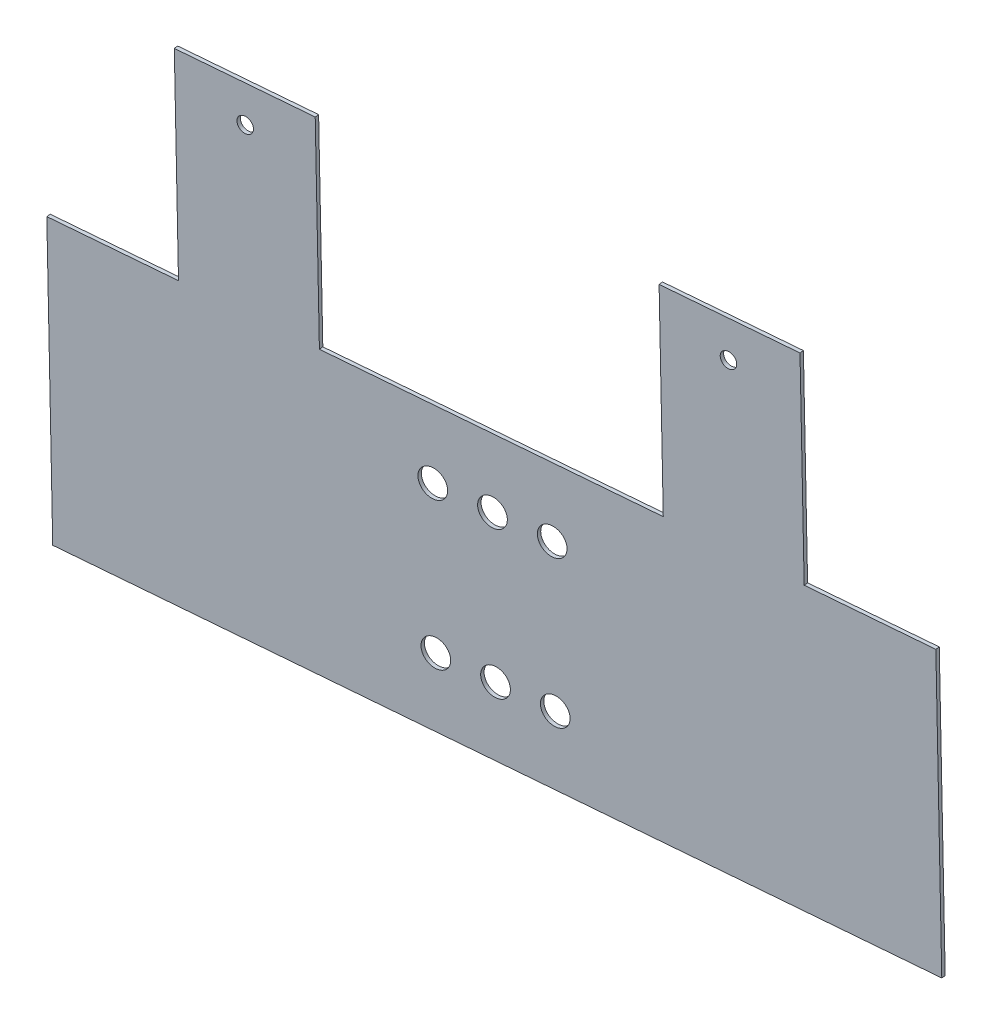
SolidWorks part; units mm, degrees
ref_plane "Front Plane" through (0, 0, 0) normal (0, 0, 1) x (1, 0, 0)
ref_plane "Top Plane" through (0, 0, 0) normal (0, 1, 0) x (1, 0, 0)
ref_plane "Right Plane" through (0, 0, 0) normal (1, 0, 0) x (0, 0, -1)
sketch "Sketch1" plane through (16.9972, -4.1499, 204.6314) normal (-0.0828, 0.0202, -0.9964) x (0.9966, 0.002, -0.0827)
  line L0 (-405.6316, 283.217) -> (-385.6926, 283.217)
  line L1 (-520.3126, 330.217) -> (-500.3736, 330.217)
  line L2 (-520.3126, 330.217) -> (-520.3126, 283.217)
  line L3 (-520.3126, 283.217) -> (-500.3736, 283.217)
  line L4 (-385.6926, 330.217) -> (-385.6926, 283.217)
  line L6 (-426.9676, 283.217) -> (-426.9676, 250.0037)
  line L7 (-426.9676, 250.0037) -> (-405.6316, 250.0037)
  line L8 (-405.6316, 283.217) -> (-405.6316, 250.0037)
  line L9 (-405.0144, 330.217) -> (-385.6926, 330.217)
  line L14 (-479.4985, 330.217) -> (-465.3599, 330.217)
  line L20 (-500.3736, 283.217) -> (-500.3736, 250.0037)
  line L21 (-500.3736, 250.0037) -> (-479.0376, 250.0037)
  line L22 (-479.0376, 283.217) -> (-479.0376, 250.0037)
  line L23 (-479.0376, 283.217) -> (-426.9676, 283.217)
  line L24 (-432.4144, 330.217) -> (-405.0144, 330.217)
  line L25 (-500.3736, 330.217) -> (-479.4985, 330.217)
  line L26 (-445.0971, 330.217) -> (-432.4144, 330.217)
  line L31 (-465.3599, 330.217) -> (-445.0971, 330.217)
  dimension "D1" = 134.62
  dimension "D2" = 47
  dimension "D3" = 21.336
  dimension "D4" = 52.07
  dimension "D5" = 33.2133
extrude "Boss-Extrude1" add sketch "Sketch1" along normal blind 0.6096
ref_plane "Plane1" through (-508.5923, -1, 42.2247) normal (0.9966, 0.002, -0.0827) x (-0.0828, 0.028, -0.9962)
sketch "Sketch5" plane through (16.9468, -4.1376, 204.024) normal (-0.0828, 0.0202, -0.9964) x (-0.9966, -0.0017, 0.0827)
  circle A0 centre (461.9962, -318.9871) radius 2.25
  circle A1 centre (452.9566, -318.9845) radius 2.25
  circle A2 centre (443.9171, -318.982) radius 2.25
  dimension "D1" = 4.5
extrude "Cut-Extrude2" cut sketch "Sketch5" against normal up to surface (0.6096 mm away) up to face at (-434.3727, -284.9591, 236.4285)
ref_plane "Plane2" through (0.0861, -306.6538, -6.2261) normal (0.0003, -0.9998, -0.0203) x (-1, -0.0003, 0)
mirror "Mirror1" about plane through (0.0861, -306.6538, -6.2261) normal (0.0003, -0.9998, -0.0203) of "Cut-Extrude2"
sketch "Sketch6" plane through (16.9468, -4.1376, 204.024) normal (-0.0828, 0.0202, -0.9964) x (-0.9966, -0.0017, 0.0827)
  circle A1 centre (416.5068, -256.1738) radius 1.25
  dimension "D1" = 2.5
extrude "Cut-Extrude5" cut sketch "Sketch6" against normal up to surface (0.6096 mm away) up to face at (-445.6631, -299.5717, 237.07)
ref_plane "Plane3" through (-451.4485, -0.8877, 37.4805) normal (-0.9966, -0.002, 0.0827) x (0.0827, 0.0002, 0.9966)
sketch "Sketch7" plane through (16.9468, -4.1376, 204.024) normal (-0.0828, 0.0202, -0.9964) x (-0.9966, -0.0017, 0.0827)
  circle A0 centre (489.6815, -256.1944) radius 1.25
extrude "Cut-Extrude6" cut sketch "Sketch7" against normal up to surface (0.6096 mm away) up to face at (-399.3264, -260.97, 234.004)
